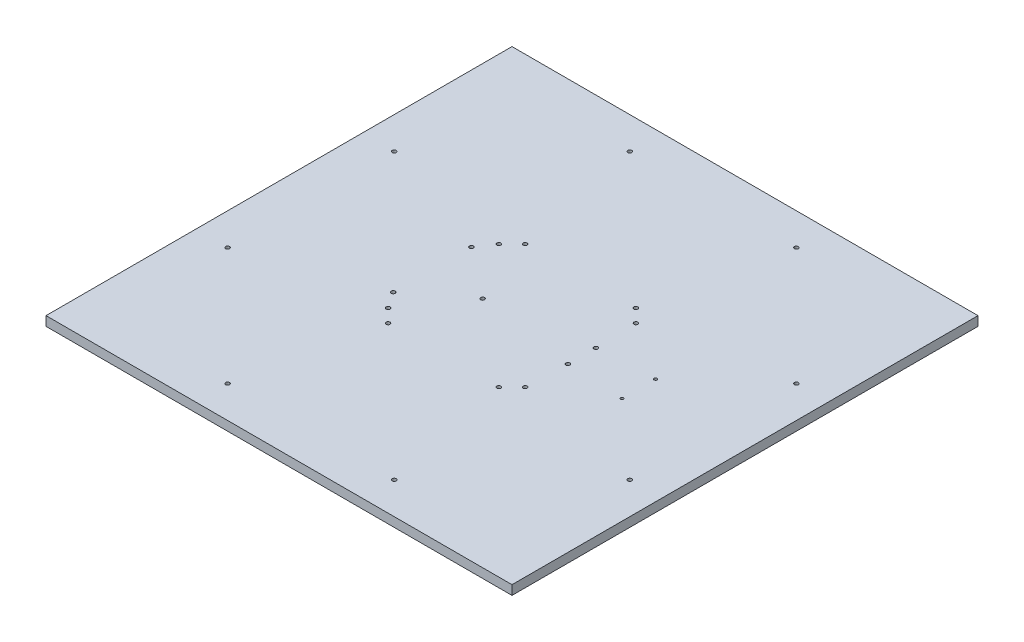
SolidWorks part; units mm, degrees
ref_plane "Plan de face" through (0, 0, 0) normal (0, 0, 1) x (1, 0, 0)
ref_plane "Plan de dessus" through (0, 0, 0) normal (0, 1, 0) x (1, 0, 0)
ref_plane "Plan de droite" through (0, 0, 0) normal (1, 0, 0) x (0, 0, -1)
sketch "Esquisse1" plane through (0, 0, 0) normal (0, 1, 0) x (1, 0, 0)
  line L1 (-250, 250) -> (250, 250)
  line L2 (-250, 250) -> (-250, -250)
  line L3 (-250, -250) -> (250, -250)
  line L4 (250, 250) -> (250, -250)
  line L5 (-250, 250) -> (250, -250) construction
  line L6 (-250, -250) -> (250, 250) construction
  point P0 (0, 0)
  dimension "D1" = 500
extrude "Boss.-Extru.1" add sketch "Esquisse1" along normal blind 10
ref_axis "Axe1" through (0, -0.5, 0) along (0, 1, 0)
sketch "Esquisse2" plane through (0, 0, 0) normal (0, 1, 0) x (1, 0, 0)
  line L0 (0, 0) -> (0, 250) construction
  line L1 (250, 250) -> (-250, 250) construction
  line L2 (0, 0) -> (89.3566, 215.7259) construction
  circle A0 centre (89.3566, 215.7259) radius 2.1
  dimension "D2" = 4.2
  dimension "D1" = 22.5
  dimension "D3" = 233.5
extrude "Enlèv. mat.-Extru.1" cut sketch "Esquisse2" along normal through all
pattern_circular "Répétition circulaire1" count 8 over 360 about axis through (0, -0.5, 0) along (0, 1, 0) of "Enlèv. mat.-Extru.1"
sketch "Esquisse3" plane through (0, 0, 0) normal (0, 1, 0) x (1, 0, 0)
  line L0 (0, 0) -> (66.468, 66.468) construction
  line L1 (59.397, 73.5391) -> (73.5391, 59.397) construction
  line L2 (0, 0) -> (59.4547, 0) construction
  circle A0 centre (59.397, 73.5391) radius 2.1
  circle A1 centre (73.5391, 59.397) radius 2.1
  dimension "D3" = 4.2
  dimension "D1" = 20
  dimension "D2" = 94
  dimension "D4" = 45
extrude "Enlèv. mat.-Extru.2" cut sketch "Esquisse3" along normal through all
pattern_circular "Répétition circulaire2" count 4 over 360 about axis through (0, -0.5, 0) along (0, 1, 0) of "Enlèv. mat.-Extru.2"
sketch "Esquisse4" plane through (0, 0, 0) normal (0, 1, 0) x (1, 0, 0)
  line L3 (0, 0) -> (-90.7447, 0) construction
  circle A0 centre (-85.5, 42) radius 2.1
  circle A1 centre (-85.5, -42) radius 2.1
  circle A2 centre (-31.5, 0) radius 2.1
  dimension "D1" = 4.2
  dimension "D2" = 31.5
  dimension "D3" = 85.5
  dimension "D4" = 84
extrude "Enlèv. mat.-Extru.3" cut sketch "Esquisse4" along normal through all
sketch "Esquisse5" plane through (0, 0, 0) normal (0, -1, 0) x (1, 0, 0)
  line L0 (0, 0) -> (136, 0) construction
  line L1 (136, -18) -> (136, 18) construction
  circle A0 centre (136, -18) radius 1.6
  circle A1 centre (136, 18) radius 1.6
  dimension "D2" = 3.2
  dimension "D1" = 36
  dimension "D3" = 136
extrude "Enlèv. mat.-Extru.4" cut sketch "Esquisse5" against normal through all
sketch "Esquisse6" plane through (0, 10, 0) normal (0, 1, 0) x (1, 0, 0)
  line L0 (0, 0) -> (75, 0) construction
  line L1 (75, 15) -> (75, -15) construction
  circle A0 centre (75, 15) radius 2.1
  circle A1 centre (75, -15) radius 2.1
  dimension "D3" = 4.2
  dimension "D1" = 75
  dimension "D2" = 30
extrude "Enlèv. mat.-Extru.7" cut sketch "Esquisse6" against normal through all
